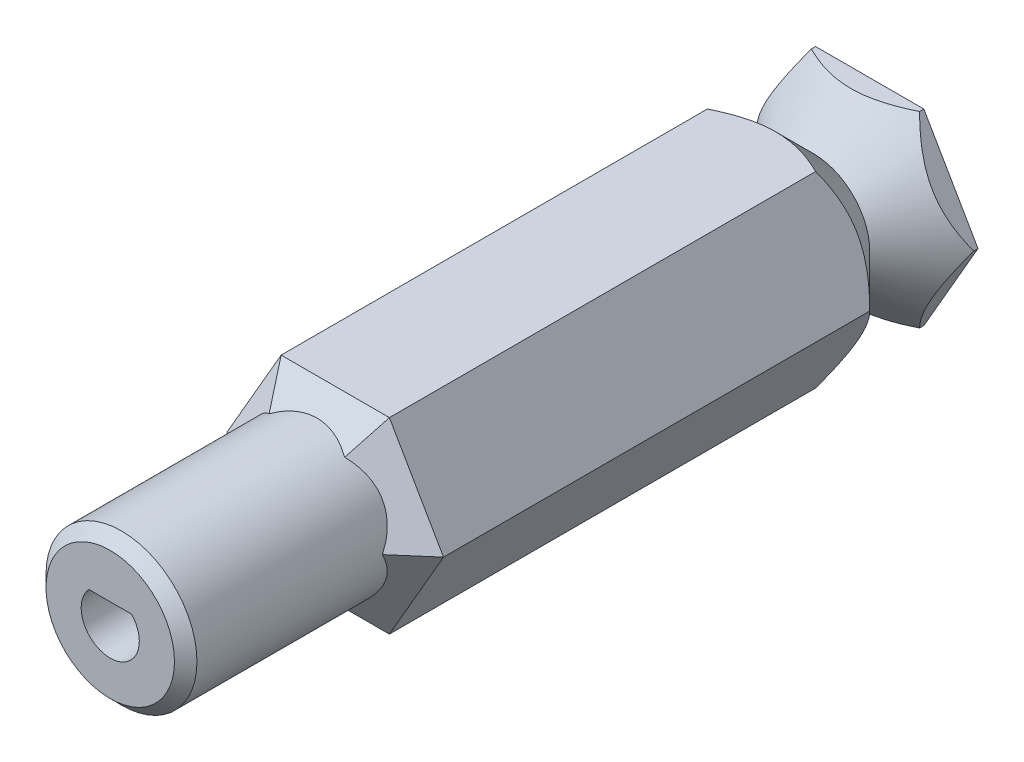
SolidWorks part; units mm, degrees
ref_plane "前视基准面" through (0, 0, 0) normal (0, 0, 1) x (1, 0, 0)
ref_plane "上视基准面" through (0, 0, 0) normal (0, 1, 0) x (1, 0, 0)
ref_plane "右视基准面" through (0, 0, 0) normal (1, 0, 0) x (0, 0, -1)
sketch "草图1" plane through (0, 0, 0) normal (0, 0, 1) x (1, 0, 0)
  line L1 (5.7735, 0) -> (2.8868, 5)
  line L2 (2.8868, 5) -> (-2.8868, 5)
  line L3 (-2.8868, 5) -> (-5.7735, 0)
  line L4 (-5.7735, 0) -> (-2.8868, -5)
  line L5 (-2.8868, -5) -> (2.8868, -5)
  line L6 (2.8868, -5) -> (5.7735, 0)
  circle A0 centre (0, 0) radius 5 construction
  dimension "D1" = 10
extrude "凸台-拉伸1" add sketch "草图1" along normal blind 30
sketch "草图2" plane through (0, 0, 30) normal (0, 0, 1) x (1, 0, 0)
  circle A0 centre (0, 0) radius 4.025
  dimension "D1" = 8.05
extrude "凸台-拉伸2" add sketch "草图2" along normal blind 10.5
chamfer "倒角1" distance 0.6 angle 45 1 edges at (4.025, 0, 40.5)
sketch "草图3" plane through (0, 0, 40.5) normal (0, 0, 1) x (1, 0, 0)
  line L0 (-1.1402, 1.05) -> (1.1402, 1.05)
  arc A0 (-1.1402, 1.05) -> (1.1402, 1.05) centre (0, 0) ccw
  dimension "D1" = 3.1
  dimension "D2" = 1.05
extrude "切除-拉伸1" cut sketch "草图3" against normal blind 8
ref_plane "基准面4" through (0, 0, 15) normal (0, 0, 1) x (1, 0, 0)
chamfer "倒角2" distance 1.5 angle 45 6 edges at (-4.3301, 2.5, 30) (-4.3301, -2.5, 30) (0, -5, 30) (4.3301, -2.5, 30) (4.3301, 2.5, 30) (0, 5, 30)
sketch "草图4" plane through (0, 0, 0) normal (1, 0, 0) x (0, 0, -1)
  line L4 (-6.5, 6.5) -> (0.5, 6.5)
  line L6 (0.5, 6.5) -> (-3, 3)
  line L7 (-3, 3) -> (-6.5, 6.5)
  line L8 (-28.5, 0) -> (0, 0) construction
  line L9 (0, 0) -> (0, 5) construction
  line L10 (6.3956, 0) -> (-8.7368, 0) construction
  line L11 (-28.5, 5) -> (0, 5) construction
  dimension "D1" = 3
  dimension "D2" = 3
  dimension "D3" = 45
  dimension "D4" = 1.5
revolve "切除-旋转4" cut sketch "草图4" angle 360 about L10
